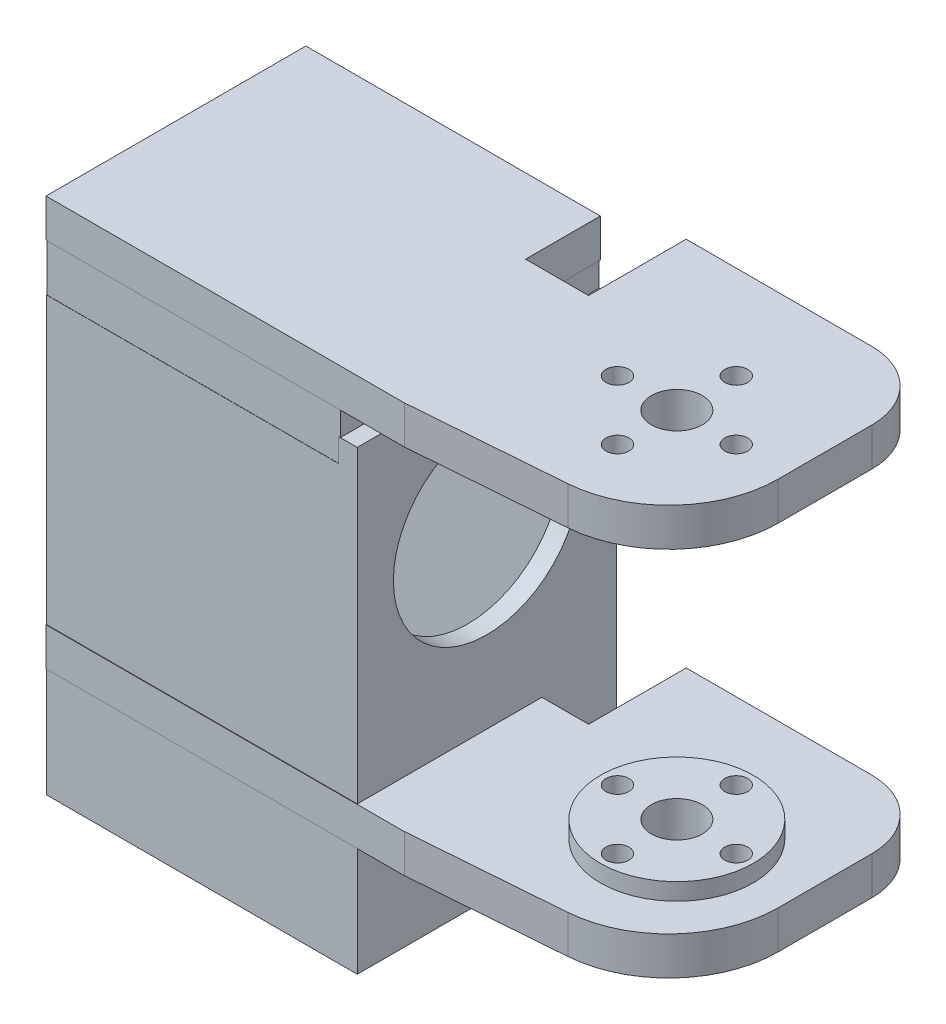
SolidWorks part; units mm, degrees
ref_plane "Front Plane" through (0, 0, 0) normal (0, 0, 1) x (1, 0, 0)
ref_plane "Top Plane" through (0, 0, 0) normal (0, 1, 0) x (1, 0, 0)
ref_plane "Right Plane" through (0, 0, 0) normal (1, 0, 0) x (0, 0, -1)
ref_plane "PY_p18_625" through (0, 18.625, 0) normal (0, 1, 0) x (1, 0, 0)
sketch "S_prism1" plane through (0, 18.625, 0) normal (0, 1, 0) x (1, 0, 0)
  line L0 (13, 10) -> (13, -1.0582)
  line L1 (1.0937, -13.9199) -> (-16.9, -15.31)
  line L2 (-16.9, -15.31) -> (-16.9, 18)
  line L3 (-16.9, 18) -> (5, 18)
  arc A0 (5, 18) -> (13, 10) centre (5.0002, 10.0002) cw
  arc A1 (13, -1.0582) -> (1.0937, -13.9199) centre (0.0999, -1.0582) cw
extrude "Boss_1" add sketch "S_prism1" along normal blind 4.5
ref_plane "PY_m20_625" through (0, -20.625, 0) normal (0, 1, 0) x (1, 0, 0)
sketch "S_cyl2" plane through (0, -20.625, 0) normal (0, 1, 0) x (1, 0, 0)
  circle A0 centre (0, 0) radius 9
  dimension "D1_S_cyl2" = 18
extrude "Boss_2" add sketch "S_cyl2" along normal blind 2
ref_plane "PY_m25_125" through (0, -25.125, 0) normal (0, 1, 0) x (1, 0, 0)
sketch "S_prism3" plane through (0, -25.125, 0) normal (0, 1, 0) x (1, 0, 0)
  line L0 (13, 10) -> (13, -1.0582)
  line L1 (1.0937, -13.9199) -> (-16.9, -15.31)
  line L2 (-16.9, -15.31) -> (-16.9, 18)
  line L3 (-16.9, 18) -> (5, 18)
  arc A0 (5, 18) -> (13, 10) centre (5.0002, 10.0002) cw
  arc A1 (13, -1.0582) -> (1.0937, -13.9199) centre (0.0999, -1.0582) cw
extrude "Boss_3" add sketch "S_prism3" along normal blind 4.5
sketch "S_prism4" plane through (0, 18.625, 0) normal (0, 1, 0) x (1, 0, 0)
  line L0 (-24.575, 6.5) -> (-16.8, 6.5)
  line L1 (-16.8, 6.5) -> (-16.8, -15.31)
  line L2 (-16.8, -15.31) -> (-24.575, -15.31)
  line L3 (-24.575, -15.31) -> (-24.575, 6.5)
extrude "Boss_4" add sketch "S_prism4" along normal blind 4.5
sketch "S_prism5" plane through (0, 18.625, 0) normal (0, 1, 0) x (1, 0, 0)
  line L0 (-59.025, -12.71) -> (-16.8, -12.71)
  line L1 (-16.8, -12.71) -> (-16.8, -15.31)
  line L2 (-16.8, -15.31) -> (-59.025, -15.31)
  line L3 (-59.025, -15.31) -> (-59.025, -12.71)
extrude "Boss_5" add sketch "S_prism5" along normal blind 4.5
sketch "S_prism6" plane through (0, 18.625, 0) normal (0, 1, 0) x (1, 0, 0)
  line L0 (-59.025, 15.31) -> (-24.325, 15.31)
  line L1 (-24.325, 15.31) -> (-24.325, -15.31)
  line L2 (-24.325, -15.31) -> (-59.025, -15.31)
  line L3 (-59.025, -15.31) -> (-59.025, 15.31)
extrude "Boss_6" add sketch "S_prism6" along normal blind 4.5
sketch "S_prism7" plane through (0, -25.125, 0) normal (0, 1, 0) x (1, 0, 0)
  line L0 (-24.575, 6.5) -> (-16.8, 6.5)
  line L1 (-16.8, 6.5) -> (-16.8, -15.31)
  line L2 (-16.8, -15.31) -> (-24.575, -15.31)
  line L3 (-24.575, -15.31) -> (-24.575, 6.5)
extrude "Boss_7" add sketch "S_prism7" along normal blind 4.5
sketch "S_prism8" plane through (0, -25.125, 0) normal (0, 1, 0) x (1, 0, 0)
  line L0 (-59.025, -12.71) -> (-16.8, -12.71)
  line L1 (-16.8, -12.71) -> (-16.8, -15.31)
  line L2 (-16.8, -15.31) -> (-59.025, -15.31)
  line L3 (-59.025, -15.31) -> (-59.025, -12.71)
extrude "Boss_8" add sketch "S_prism8" along normal blind 4.5
ref_plane "PZ_m15_260" through (0, 0, -15.26) normal (0, 0, 1) x (1, 0, 0)
sketch "S_box9" plane through (0, 0, -15.26) normal (0, 0, 1) x (1, 0, 0)
  line L0 (-59.025, 10.51) -> (-24.625, 10.51)
  line L1 (-24.625, 10.51) -> (-24.625, 13.01)
  line L2 (-24.625, 13.01) -> (-59.025, 13.01)
  line L3 (-59.025, 13.01) -> (-59.025, 10.51)
  dimension "P1" = 59.025
  dimension "P2" = 10.51
  dimension "P3" = 24.625
  dimension "P4" = 10.51
  dimension "P5" = 24.625
  dimension "P6" = 13.01
  dimension "P7" = 59.025
  dimension "P8" = 13.01
extrude "Boss_9" add sketch "S_box9" along normal blind 30.52
sketch "S_box10" plane through (0, 0, -15.26) normal (0, 0, 1) x (1, 0, 0)
  line L0 (-59.025, -38.01) -> (-24.625, -38.01)
  line L1 (-24.625, -38.01) -> (-24.625, 13.01)
  line L2 (-24.625, 13.01) -> (-59.025, 13.01)
  line L3 (-59.025, 13.01) -> (-59.025, -38.01)
  dimension "P1" = 59.025
  dimension "P2" = 38.01
  dimension "P3" = 24.625
  dimension "P4" = 38.01
  dimension "P5" = 24.625
  dimension "P6" = 13.01
  dimension "P7" = 59.025
  dimension "P8" = 13.01
extrude "Boss_10" add sketch "S_box10" along normal blind 2.5
ref_plane "PZ_p12_760" through (0, 0, 12.76) normal (0, 0, 1) x (1, 0, 0)
sketch "S_box11" plane through (0, 0, 12.76) normal (0, 0, 1) x (1, 0, 0)
  line L0 (-59.025, -38.01) -> (-24.625, -38.01)
  line L1 (-24.625, -38.01) -> (-24.625, 13.01)
  line L2 (-24.625, 13.01) -> (-59.025, 13.01)
  line L3 (-59.025, 13.01) -> (-59.025, -38.01)
  dimension "P1" = 59.025
  dimension "P2" = 38.01
  dimension "P3" = 24.625
  dimension "P4" = 38.01
  dimension "P5" = 24.625
  dimension "P6" = 13.01
  dimension "P7" = 59.025
  dimension "P8" = 13.01
extrude "Boss_11" add sketch "S_box11" along normal blind 2.5
sketch "S_box12" plane through (0, 0, -15.26) normal (0, 0, 1) x (1, 0, 0)
  line L0 (-59.025, -38.01) -> (-56.625, -38.01)
  line L1 (-56.625, -38.01) -> (-56.625, 13.01)
  line L2 (-56.625, 13.01) -> (-59.025, 13.01)
  line L3 (-59.025, 13.01) -> (-59.025, -38.01)
  dimension "P1" = 59.025
  dimension "P2" = 38.01
  dimension "P3" = 56.625
  dimension "P4" = 38.01
  dimension "P5" = 56.625
  dimension "P6" = 13.01
  dimension "P7" = 59.025
  dimension "P8" = 13.01
extrude "Boss_12" add sketch "S_box12" along normal blind 30.52
sketch "S_box13" plane through (0, 0, -15.26) normal (0, 0, 1) x (1, 0, 0)
  line L0 (-24.625, -38.01) -> (-22.4, -38.01)
  line L1 (-22.4, -38.01) -> (-22.4, 15.76)
  line L2 (-22.4, 15.76) -> (-24.625, 15.76)
  line L3 (-24.625, 15.76) -> (-24.625, -38.01)
  dimension "P1" = 24.625
  dimension "P2" = 38.01
  dimension "P3" = 22.4
  dimension "P4" = 38.01
  dimension "P5" = 22.4
  dimension "P6" = 15.76
  dimension "P7" = 24.625
  dimension "P8" = 15.76
extrude "Boss_13" add sketch "S_box13" along normal blind 30.52
ref_plane "PZ_m15_240" through (0, 0, -15.24) normal (0, 0, 1) x (1, 0, 0)
sketch "S_box14" plane through (0, 0, -15.24) normal (0, 0, 1) x (1, 0, 0)
  line L0 (-58.955, 12.9) -> (-24.395, 12.9)
  line L1 (-24.395, 12.9) -> (-24.395, 18.725)
  line L2 (-24.395, 18.725) -> (-58.955, 18.725)
  line L3 (-58.955, 18.725) -> (-58.955, 12.9)
  dimension "P1" = 58.955
  dimension "P2" = 12.9
  dimension "P3" = 24.395
  dimension "P4" = 12.9
  dimension "P5" = 24.395
  dimension "P6" = 18.725
  dimension "P7" = 58.955
  dimension "P8" = 18.725
extrude "Boss_14" add sketch "S_box14" along normal blind 30.48
ref_plane "PY_p18_525" through (0, 18.525, 0) normal (0, 1, 0) x (1, 0, 0)
sketch "S_hole15" plane through (0, 18.525, 0) normal (0, 1, 0) x (1, 0, 0)
  circle A0 centre (0, 0) radius 3
  dimension "D1_S_hole15" = 6
extrude "Hole_15" cut sketch "S_hole15" along normal blind 4.7
sketch "S_hole16" plane through (0, 18.525, 0) normal (0, 1, 0) x (1, 0, 0)
  circle A0 centre (7, 0) radius 1.35
  dimension "D1_S_hole16" = 2.7
  dimension "P2" = 7
extrude "Hole_16" cut sketch "S_hole16" along normal blind 4.7
sketch "S_hole17" plane through (0, 18.525, 0) normal (0, 1, 0) x (1, 0, 0)
  circle A0 centre (0, -7) radius 1.35
  dimension "D1_S_hole17" = 2.7
  dimension "P2" = 7
extrude "Hole_17" cut sketch "S_hole17" along normal blind 4.7
sketch "S_hole18" plane through (0, 18.525, 0) normal (0, 1, 0) x (1, 0, 0)
  circle A0 centre (-7, 0) radius 1.35
  dimension "D1_S_hole18" = 2.7
  dimension "P2" = 7
extrude "Hole_18" cut sketch "S_hole18" along normal blind 4.7
sketch "S_hole19" plane through (0, 18.525, 0) normal (0, 1, 0) x (1, 0, 0)
  circle A0 centre (0, 7) radius 1.35
  dimension "D1_S_hole19" = 2.7
  dimension "P2" = 7
extrude "Hole_19" cut sketch "S_hole19" along normal blind 4.7
ref_plane "PY_m25_225" through (0, -25.225, 0) normal (0, 1, 0) x (1, 0, 0)
sketch "S_hole20" plane through (0, -25.225, 0) normal (0, 1, 0) x (1, 0, 0)
  circle A0 centre (0, 0) radius 3
  dimension "D1_S_hole20" = 6
extrude "Hole_20" cut sketch "S_hole20" along normal blind 6.7
sketch "S_hole21" plane through (0, -25.225, 0) normal (0, 1, 0) x (1, 0, 0)
  circle A0 centre (7, 0) radius 1.35
  dimension "D1_S_hole21" = 2.7
  dimension "P2" = 7
extrude "Hole_21" cut sketch "S_hole21" along normal blind 6.7
sketch "S_hole22" plane through (0, -25.225, 0) normal (0, 1, 0) x (1, 0, 0)
  circle A0 centre (0, -7) radius 1.35
  dimension "D1_S_hole22" = 2.7
  dimension "P2" = 7
extrude "Hole_22" cut sketch "S_hole22" along normal blind 6.7
sketch "S_hole23" plane through (0, -25.225, 0) normal (0, 1, 0) x (1, 0, 0)
  circle A0 centre (-7, 0) radius 1.35
  dimension "D1_S_hole23" = 2.7
  dimension "P2" = 7
extrude "Hole_23" cut sketch "S_hole23" along normal blind 6.7
sketch "S_hole24" plane through (0, -25.225, 0) normal (0, 1, 0) x (1, 0, 0)
  circle A0 centre (0, 7) radius 1.35
  dimension "D1_S_hole24" = 2.7
  dimension "P2" = 7
extrude "Hole_24" cut sketch "S_hole24" along normal blind 6.7
ref_plane "PX_m59_125" through (-59.125, 0, 0) normal (1, 0, 0) x (0, 0, -1)
sketch "S_hole25" plane through (-59.125, 0, 0) normal (1, 0, 0) x (0, 0, -1)
  circle A0 centre (0, 0) radius 11
  dimension "D1_S_hole25" = 22
extrude "Hole_25" cut sketch "S_hole25" along normal blind 2.6
sketch "S_hole26" plane through (-59.125, 0, 0) normal (1, 0, 0) x (0, 0, -1)
  circle A0 centre (-10.25, -8.3) radius 1.1
  dimension "D1_S_hole26" = 2.2
  dimension "P2" = 10.25
  dimension "P3" = 8.3
extrude "Hole_26" cut sketch "S_hole26" along normal blind 2.6
sketch "S_hole27" plane through (-59.125, 0, 0) normal (1, 0, 0) x (0, 0, -1)
  circle A0 centre (10.25, -32.75) radius 1.1
  dimension "D1_S_hole27" = 2.2
  dimension "P2" = 10.25
  dimension "P3" = 32.75
extrude "Hole_27" cut sketch "S_hole27" along normal blind 2.6
sketch "S_hole28" plane through (-59.125, 0, 0) normal (1, 0, 0) x (0, 0, -1)
  circle A0 centre (-10.25, -32.75) radius 1.1
  dimension "D1_S_hole28" = 2.2
  dimension "P2" = 10.25
  dimension "P3" = 32.75
extrude "Hole_28" cut sketch "S_hole28" along normal blind 2.6
ref_plane "PX_m24_725" through (-24.725, 0, 0) normal (1, 0, 0) x (0, 0, -1)
sketch "S_hole29" plane through (-24.725, 0, 0) normal (1, 0, 0) x (0, 0, -1)
  circle A0 centre (0, 0) radius 11
  dimension "D1_S_hole29" = 22
extrude "Hole_29" cut sketch "S_hole29" along normal blind 2.425
sketch "S_pcut30" plane through (-59.125, 0, 0) normal (1, 0, 0) x (0, 0, -1)
  line L0 (15.86, -38.61) -> (15.86, -28.41)
  line L1 (15.86, -28.41) -> (5.66, -38.61)
  line L2 (5.66, -38.61) -> (15.86, -38.61)
extrude "Cut_30" cut sketch "S_pcut30" along normal blind 34.6
equation "\"plate_t\" = 3"
equation "\"clearance\" = 0.4"
